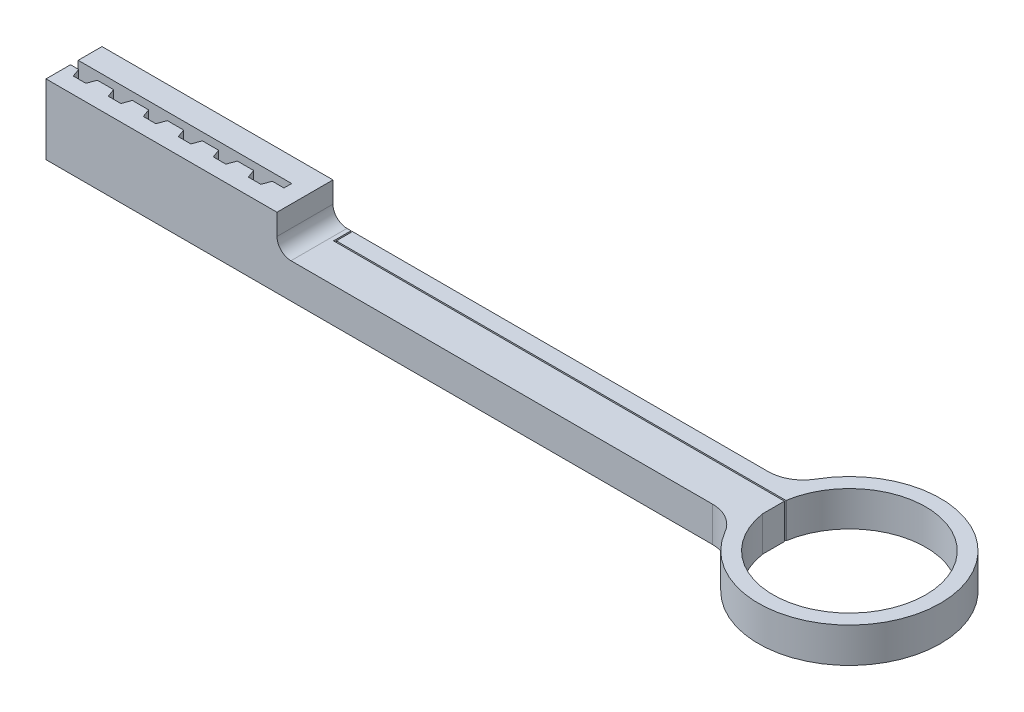
SolidWorks part; units mm, degrees
ref_plane "Спереди" through (0, 0, 0) normal (0, 0, 1) x (1, 0, 0)
ref_plane "Сверху" through (0, 0, 0) normal (0, 1, 0) x (1, 0, 0)
ref_plane "Справа" through (0, 0, 0) normal (1, 0, 0) x (0, 0, -1)
sketch "Эскиз1" plane through (0, 0, 0) normal (0, 1, 0) x (1, 0, 0)
  circle A0 centre (0, 0) radius 10.9
  circle A1 centre (0, 0) radius 13
  dimension "D1" = 21.8
  dimension "D2" = 26
extrude "ring" add sketch "Эскиз1" along normal blind 5
sketch "Эскиз2" plane through (0, 0, 0) normal (0, 1, 0) x (1, 0, 0)
  line L0 (34.0214, 0) -> (-42.1067, 0) construction
  line L2 (-10.7819, 4) -> (-110.7819, 4)
  line L3 (-10.7819, 4) -> (-10.7819, -4)
  line L4 (-10.7819, -4) -> (-110.7819, -4)
  line L5 (-110.7819, 4) -> (-110.7819, -4)
  circle A0 centre (0, 0) radius 11.5 construction
  point P9 (-10.7819, 0)
  dimension "D3" = 23
  dimension "D2" = 8
  dimension "D4" = 100
extrude "stick" add sketch "Эскиз2" along normal blind 5
sketch "Эскиз3" plane through (0, 0, 0) normal (0, 1, 0) x (1, 0, 0)
  line L0 (-110.7819, -4) -> (-12.3693, -4) construction
  line L1 (-110.7819, 4) -> (-77.7819, 4)
  line L2 (-110.7819, 4) -> (-110.7819, -4)
  line L3 (-110.7819, -4) -> (-77.7819, -4)
  line L4 (-77.7819, 4) -> (-77.7819, -4)
  dimension "D1" = 33
extrude "key" add sketch "Эскиз3" along normal blind 10
fillet "Скругление1" radius 5 2 edges at (-12.3693, 2.5, 4) (-12.3693, 2.5, -4)
ref_plane "Плоскость1" through (0, 2.5, 0) normal (0, 1, 0) x (-1, 0, 0)
sketch "Эскиз4" plane through (0, 2.5, 0) normal (0, 1, 0) x (1, 0, 0)
  line L0 (-110.7819, 0) -> (-77.7819, 0) construction
  line L1 (-110.7819, 4) -> (-110.7819, -4) construction
  line L2 (-77.7819, -4) -> (-77.7819, 4) construction
  line L3 (-110.7819, 0.6) -> (-80.2819, 0.6)
  line L4 (-109.1819, -1.7) -> (-107.3819, -1.7)
  line L5 (-109.6187, -0.5) -> (-90.7763, -0.5) construction
  line L6 (-109.6187, -0.5) -> (-109.1819, -1.7) construction
  line L7 (-109.6187, -0.5) -> (-109.1819, -1.7)
  line L8 (-107.3819, -1.7) -> (-106.9452, -0.5)
  line L9 (-108.2819, 1.0157) -> (-108.2819, -3.4603) construction
  line L10 (-109.6187, -0.5) -> (-110.7819, -0.5)
  line L11 (-106.9452, -0.5) -> (-105.7819, -0.5)
  line L12 (-110.7819, 0.6) -> (-110.7819, -0.5)
  line L13 (-104.6187, -0.5) -> (-105.7819, -0.5)
  line L14 (-104.1819, -1.7) -> (-102.3819, -1.7)
  line L15 (-102.3819, -1.7) -> (-101.9452, -0.5)
  line L16 (-101.9452, -0.5) -> (-100.7819, -0.5)
  line L17 (-104.6187, -0.5) -> (-104.1819, -1.7)
  line L18 (-99.6187, -0.5) -> (-100.7819, -0.5)
  line L19 (-99.1819, -1.7) -> (-97.3819, -1.7)
  line L20 (-97.3819, -1.7) -> (-96.9452, -0.5)
  line L21 (-96.9452, -0.5) -> (-95.7819, -0.5)
  line L22 (-99.6187, -0.5) -> (-99.1819, -1.7)
  line L24 (-94.6187, -0.5) -> (-95.7819, -0.5)
  line L25 (-94.1819, -1.7) -> (-92.3819, -1.7)
  line L26 (-92.3819, -1.7) -> (-91.9452, -0.5)
  line L27 (-91.9452, -0.5) -> (-90.7819, -0.5)
  line L28 (-94.6187, -0.5) -> (-94.1819, -1.7)
  line L43 (-89.6187, -0.5) -> (-90.7819, -0.5)
  line L44 (-89.1819, -1.7) -> (-87.3819, -1.7)
  line L45 (-87.3819, -1.7) -> (-86.9452, -0.5)
  line L46 (-86.9452, -0.5) -> (-85.7819, -0.5)
  line L47 (-89.6187, -0.5) -> (-89.1819, -1.7)
  line L48 (-84.6187, -0.5) -> (-85.7819, -0.5)
  line L49 (-84.1819, -1.7) -> (-82.3819, -1.7)
  line L50 (-82.3819, -1.7) -> (-81.9452, -0.5)
  line L51 (-81.9452, -0.5) -> (-80.7819, -0.5)
  line L52 (-84.6187, -0.5) -> (-84.1819, -1.7)
  line L53 (-80.7819, -0.5) -> (-80.2819, -0.5)
  line L54 (-80.2819, 0.6) -> (-80.2819, -0.5)
  point P12 (-108.2819, -1.7)
  dimension "D1" = 1.8
  dimension "D2" = 0.6
  dimension "D3" = 0.5
  dimension "D4" = 1.2
  dimension "D5" = 110
  dimension "D6" = 5
  dimension "D7" = 40
  dimension "D8" = 0.5
fillet "Скругление5" radius 2 1 edges at (-77.7819, 5, 0)
extrude "key hole" cut sketch "Эскиз4" against normal through all and the other way through all
sketch "Эскиз5" plane through (0, 0, 0) normal (0, -1, 0) x (1, 0, 0)
  line L0 (0, 0) -> (-70.3859, 0) construction
  line L1 (-75.2, -4) -> (-75.2, -1.5)
  line L3 (-75.2, -1.5) -> (0, -1.5)
  line L4 (0, -1.5) -> (0, -1.7)
  line L5 (0, -1.7) -> (-75, -1.7)
  line L6 (-75, -1.7) -> (-75, -4)
  line L7 (-75, -4) -> (-75.2, -4)
  line L8 (-15.5885, -4) -> (-110.7819, -4) construction
  dimension "D1" = 0.2
  dimension "D2" = 0.2
  dimension "D3" = 75
  dimension "D4" = 1.5
extrude "Вытянуть2" cut sketch "Эскиз5" against normal through all
